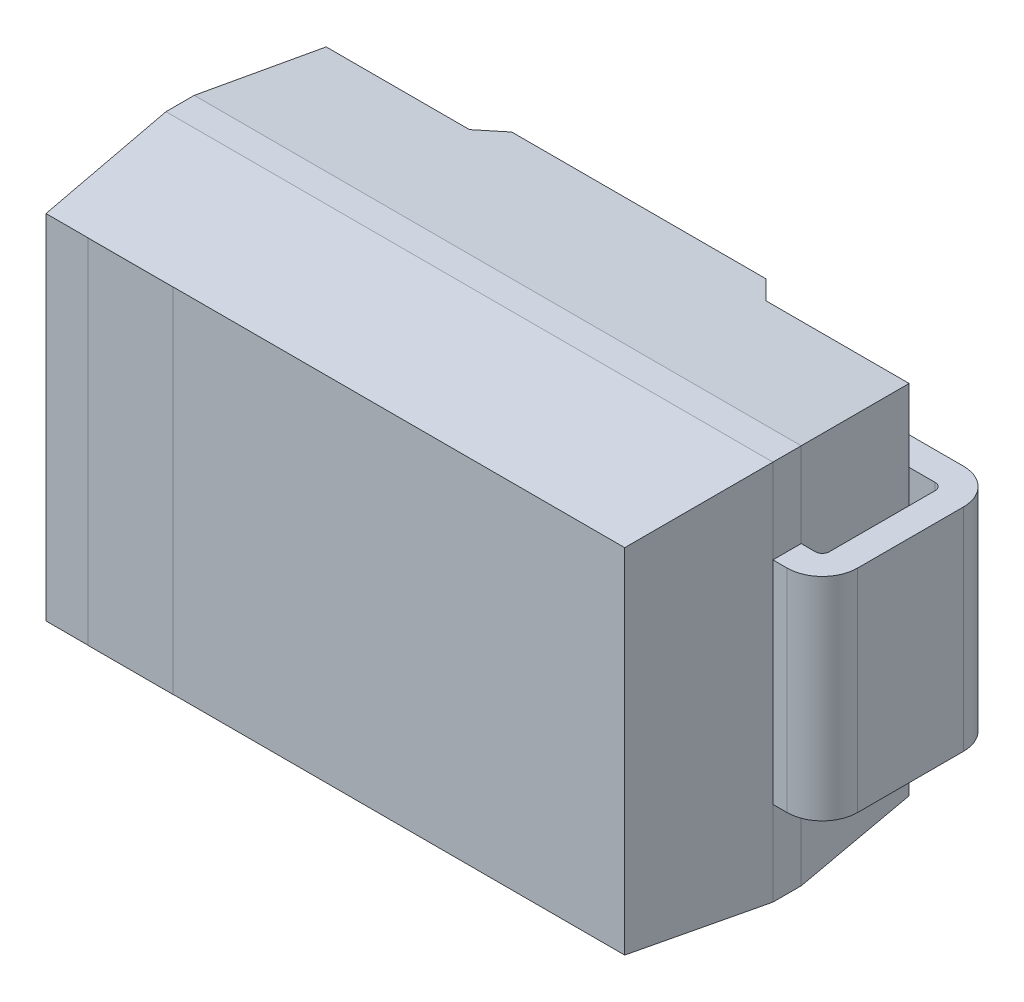
SolidWorks part; units mm, degrees
ref_plane "Płaszczyzna przednia" through (0, 0, 0) normal (0, 0, 1) x (1, 0, 0)
ref_plane "Płaszczyzna górna" through (0, 0, 0) normal (0, 1, 0) x (1, 0, 0)
ref_plane "Płaszczyzna prawa" through (0, 0, 0) normal (1, 0, 0) x (0, 0, -1)
sketch "Szkic1" plane through (0, 0, 0) normal (0, 0, 1) x (1, 0, 0)
  line L1 (2.15, -1.35) -> (-2.15, -1.35)
  line L2 (2.15, -1.35) -> (2.15, 1.35)
  line L3 (2.15, 1.35) -> (-2.15, 1.35)
  line L4 (-2.15, -1.35) -> (-2.15, 1.35)
  line L5 (2.15, -1.35) -> (-2.15, 1.35) construction
  line L6 (2.15, 1.35) -> (-2.15, -1.35) construction
  point P0 (0, 0)
  dimension "D1" = 4.3
  dimension "D2" = 2.7
extrude "Dodanie-wyciągnięcie1" add sketch "Szkic1" along normal blind 2.15
chamfer "Sfazowanie1" distance 0.95 distance2 0.1 4 edges at (0, 1.35, 2.15) (2.15, 0, 2.15) (0, -1.35, 2.15) (-2.15, 0, 2.15) first distance on face at (0, 1.35, 1.075) first distance on face at (2.15, 0, 1.075) first distance on face at (0, -1.35, 1.075) first distance on face at (-2.15, 0, 1.075)
chamfer "Sfazowanie2" distance 0.1 distance2 1 4 edges at (0, 1.35, 0) (2.15, 0, 0) (0, -1.35, 0) (-2.15, 0, 0) first distance on face at (0, 0, 0)
sketch "Szkic2" plane through (0, 0, 2.15) normal (0, 0, 1) x (1, 0, 0)
  line L0 (-1.75, 1.25) -> (-1.75, -1.25)
  line L1 (-1.15, 1.25) -> (-1.15, -1.25)
  line L4 (-1.15, 1.25) -> (-1.75, 1.25)
  line L5 (-1.75, -1.25) -> (-1.15, -1.25)
  line L6 (-2.05, 1.25) -> (-2.05, -1.25) construction
  line L8 (2.05, 1.25) -> (-2.05, 1.25) construction
  dimension "D1" = 0.3
  dimension "D2" = 0.6
  dimension "D3" = 2.5
extrude "Dodanie-wyciągnięcie2" add sketch "Szkic2" along normal blind 0.001
sketch "Szkic3" plane through (-2.15, 0, 0) normal (-1, 0, 0) x (0, 0, 1)
  line L0 (1.2, 1.35) -> (1, 1.35) construction
  line L1 (0, 1.35) -> (0.15, 1.35)
  line L2 (0, 1.35) -> (0, -1.35)
  line L3 (0, -1.35) -> (0.15, -1.35)
  line L4 (0.15, 1.35) -> (0.15, -1.35)
  line L5 (1.2, -1.35) -> (1, -1.35) construction
  line L6 (1, 1.35) -> (1, -1.35) construction
  dimension "D1" = 0.85
  dimension "D2" = 0.15
extrude "Wytnij-wyciągnięcie1" cut sketch "Szkic3" against normal blind 1.1
sketch "Szkic4" plane through (-2.15, 0, 0) normal (-1, 0, 0) x (0, 0, 1)
  line L0 (1.2, -1.35) -> (1.2, 1.35) construction
  line L1 (1.2, 0.75) -> (1, 0.75)
  line L2 (1.2, 0.75) -> (1.2, -0.75)
  line L3 (1.2, -0.75) -> (1, -0.75)
  line L4 (1, 0.75) -> (1, -0.75)
  line L5 (1, 1.35) -> (1, -1.35) construction
  line L6 (1.2, 1.35) -> (1, 1.35) construction
  line L9 (1.2, 0) -> (1, 0) construction
  dimension "D1" = 1.5
  dimension "D2" = 0.6
  dimension "D3" = 0.2
sketch "Szkic6" plane through (0, 0, 0) normal (0, 1, 0) x (1, 0, 0)
  line L0 (-2.15, -1.2) -> (-2.25, -1.2)
  line L1 (-2.5, -0.95) -> (-2.5, -0.2)
  line L2 (-2.25, 0.05) -> (-1.2, 0.05)
  arc A0 (-2.5, -0.2) -> (-2.25, 0.05) centre (-2.25, -0.2) cw
  arc A1 (-2.25, -1.2) -> (-2.5, -0.95) centre (-2.25, -0.95) cw
  dimension "D1" = 0.25
  dimension "D2" = 1.2
  dimension "D3" = 2.15
  dimension "D4" = 2.5
  dimension "D5" = 0.05
  dimension "D6" = 1.2
chamfer "Sfazowanie3" distance 0.15 angle 45 1 edges at (-1.05, 0, 0)
sweep "Wyciągnięcie po ścieżce2" add profiles "Szkic4" path "Szkic6"
mirror "Lustro1" about plane through (0, 0, 0) normal (1, 0, 0) of "Sfazowanie3", "Wytnij-wyciągnięcie1", "Wyciągnięcie po ścieżce2"
